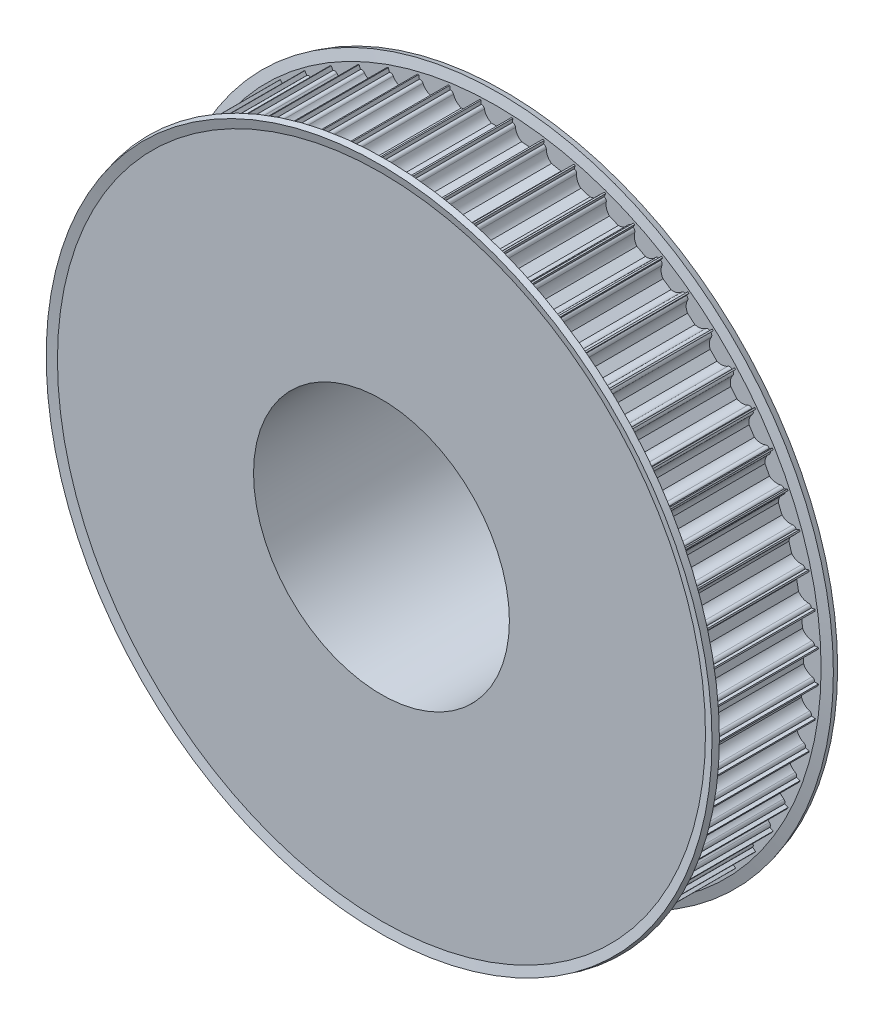
SolidWorks part; units mm, degrees
material "2219-T37"
ref_plane "Front Plane" through (0, 0, 0) normal (0, 0, 1) x (1, 0, 0)
ref_plane "Top Plane" through (0, 0, 0) normal (0, 1, 0) x (1, 0, 0)
ref_plane "Right Plane" through (0, 0, 0) normal (1, 0, 0) x (0, 0, -1)
sketch "Sketch1" plane through (0, 0, 0) normal (1, 0, 0) x (0, 0, -1)
  line L0 (0, 31.75) -> (0, 80)
  line L1 (0, 80) -> (30, 80)
  line L2 (30, 80) -> (30, 47.25)
  line L3 (30, 47.25) -> (45, 47.25)
  line L4 (45, 47.25) -> (45, 31.75)
  line L5 (45, 31.75) -> (0, 31.75)
  line L6 (-29.5361, 0) -> (53.0718, 0) construction
  dimension "D1" = 48.25
  dimension "D2" = 30
  dimension "D3" = 82.6079
  dimension "D4" = 15
  dimension "D5" = 15.5
  dimension "D6" = 45
  dimension "D7" = 31.75
revolve "Revolve1" add sketch "Sketch1" angle 360 about L6
sketch "Sketch2" plane through (0, 0, 0) normal (0, 0, 1) x (1, 0, 0)
  line L0 (3.6742, 79) -> (3.75, 79)
  line L1 (-3.75, 81) -> (3.75, 81)
  line L2 (-3.75, 81) -> (-3.75, 79)
  line L3 (-3.75, 79) -> (-3.6742, 79)
  line L4 (3.75, 81) -> (3.75, 79)
  line L5 (-1.199, 76.25) -> (1.199, 76.25)
  arc A0 (-2.9394, 78.4) -> (-1.199, 76.25) centre (0, 79) ccw
  arc A1 (-2.9394, 78.4) -> (-3.6742, 79) centre (-3.6742, 78.25) ccw
  arc A2 (2.9394, 78.4) -> (3.6742, 79) centre (3.6742, 78.25) cw
  arc A3 (1.199, 76.25) -> (2.9394, 78.4) centre (0, 79) ccw
  dimension "D1" = 3
  dimension "D5" = 0.75
  dimension "D6" = 0.75
  dimension "D2" = 2
  dimension "D3" = 7.5
  dimension "D4" = 79
  dimension "D7" = 2.75
extrude "Cut-Extrude1" cut sketch "Sketch2" against normal through all
sketch "Sketch3" plane through (0, 0, 0) normal (1, 0, 0) x (0, 0, -1)
  line L0 (-21.2099, 0) -> (61.6638, 0) construction
  dimension "D1" = 82.8737
pattern_circular "CirPattern1" count 64 over 360 about axis through (0, 0, 21.2099) along (0, 0, -1) of "Cut-Extrude1"
sketch "Sketch4" plane through (0, 0, 0) normal (1, 0, 0) x (0, 0, -1)
  line L0 (1.5, 80.6121) -> (0.0511, 80.2238) construction
  line L1 (0, 80.6121) -> (1.5, 80.6121) construction
  line L2 (0, 80.6121) -> (0, 75.6121)
  line L3 (0, 75.6121) -> (1.5, 75.6121)
  line L4 (1.5, 80.6121) -> (1.5, 75.6121)
  line L5 (1.5, 80.6121) -> (0.8569, 83.0121)
  line L6 (0.0511, 80.2238) -> (-0.592, 82.6238)
  line L7 (0.8569, 83.0121) -> (-0.592, 82.6238)
  line L8 (30, 79.9121) -> (0, 79.9121) construction
  line L9 (15, 37.195) -> (15, -35.9286) construction
  line L10 (0, 78.3106) -> (0, 76.0004) construction
  line L11 (30, 80.6121) -> (28.5, 80.6121) construction
  line L12 (28.5, 80.6121) -> (29.9489, 80.2238) construction
  line L13 (29.1431, 83.0121) -> (30.592, 82.6238)
  line L14 (29.9489, 80.2238) -> (30.592, 82.6238)
  line L15 (28.5, 80.6121) -> (29.1431, 83.0121)
  line L16 (28.5, 80.6121) -> (28.5, 75.6121)
  line L17 (30, 75.6121) -> (28.5, 75.6121)
  line L18 (30, 80.6121) -> (30, 75.6121)
  dimension "D1" = 165
  dimension "D2" = 5
  dimension "D3" = 1.5
  dimension "D4" = 2.4
  dimension "D5" = 1.5
  dimension "D6" = 0.7
  dimension "D7" = 73.1236
  dimension "D8" = 0
revolve "Revolve2" add sketch "Sketch4" angle 360 about L0 region at (0, 79.2432, -0.6556) region at (0, 79.2432, -29.3444)
